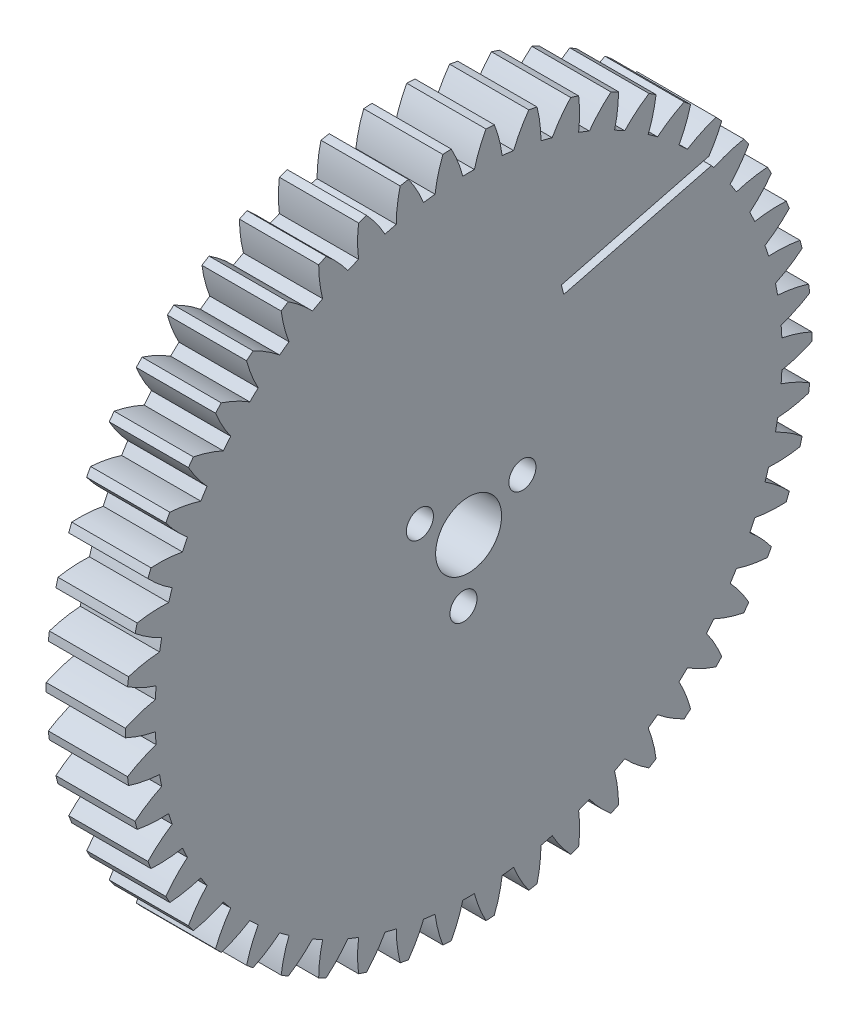
SolidWorks part; units mm, degrees
ref_plane "Plane1" through (0, 0, 0) normal (0, 0, 1) x (1, 0, 0)
ref_plane "Plane2" through (0, 0, 0) normal (0, 1, 0) x (1, 0, 0)
ref_plane "Plane3" through (0, 0, 0) normal (1, 0, 0) x (0, 0, -1)
sketch "HoldingSke" plane through (0, 0, 0) normal (0, 1, 0) x (1, 0, 0)
  line L0 (0, 0) -> (0.6428, -0.766)
  line L1 (-15, 0) -> (100, 0) construction
  line L2 (0, 0) -> (-2.1039, 2.3779)
  line L3 (0, 0) -> (-11.863, 4.5341)
  line L4 (0, 0) -> (5.5511, 6.6156)
  line L5 (0, 0) -> (-46.8476, -17.4728)
  line L6 (0, 0) -> (-3.3159, -2.2372)
  line L7 (-2.1039, 2.3779) -> (8.6586, 51.2059)
  line L8 (-76.2, 54.61) -> (-75.3, 54.61)
  line L9 (-71.009, 38.7566) -> (-53.1078, 45.2721)
  line L10 (-76.2, 71.12) -> (104.1128, 71.12)
  line L11 (0, 0) -> (-4, 0)
  line L12 (-76.2, 101.6) -> (-76.162, 101.6)
  line L13 (24.9733, 27.94) -> (52.9518, 28.4284)
  line L14 (24.9733, 27.94) -> (24.9743, 27.94)
  line L15 (24.9733, 27.94) -> (100.4006, 29.5858)
  line L16 (-63.627, -1) -> (-12.827, -1)
  circle A0 centre (0, 0) radius 2.5
  circle A1 centre (0, 0) radius 23.749
  circle A2 centre (0, 0) radius 37.5
  circle A3 centre (0, 0) radius 2.5
  dimension "MHD" = 47.498
  dimension "Hub_dia" = 75
  dimension "Bore" = 5
  dimension "MBD" = 5
  dimension "Num_teeth" = 50
  dimension "Pitch_radius" = 180.3128
  dimension "Pitch" = 1
  dimension "Width" = 4
  dimension "Overall_len" = 50
  dimension "Show_teeth" = 50
  dimension "Thickness" = 4
  dimension "OAL" = 50.0001
  dimension "T_dim" = 0.9
  dimension "Ap" = 20
  dimension "H" = 19.05
  dimension "Backlash" = 0.038
  dimension "Addendum_fac" = 1
  dimension "Dedendum_fac" = 1.25
  dimension "Clearance_fac" = 0.25
  dimension "Dedendum_add" = 0.001
  dimension "Module" = 1
sketch "BasProSke" plane through (0, 0, 0) normal (0, 1, 0) x (1, 0, 0)
  line L0 (-10, 0) -> (60, 0) construction
  line L1 (0, 0) -> (0, 26)
  line L2 (0, 0) -> (6, 0)
  line L3 (6, 0) -> (6, 26)
  line L4 (6, 26) -> (0, 26)
  dimension "Diameter" = 52
  dimension "Thickness" = 6
revolve "Base-Revolve" add sketch "BasProSke" angle 360 about L0
sketch "TooCutSke" plane through (0, 0, 0) normal (1, 0, 0) x (0, 0, -1)
  line L1 (0, 0) -> (0, 107) construction
  line L2 (0, 0) -> (-0.8518, 24.9855) construction
  line L3 (0, 0) -> (-3.1382, 49.8807) construction
  line L4 (-0.8518, 24.9855) -> (-1.5691, 24.9404) construction
  arc A0 (0.4377, 23.745) -> (-0.4377, 23.745) centre (0, 0) ccw
  arc A1 (1.3294, 25.9914) -> (-1.3294, 25.9914) centre (0, 0) ccw
  circle A2 centre (0, 0) radius 25 construction
  circle A3 centre (0, 0) radius 23.4923 construction
  arc A4 (-0.4377, 23.745) -> (-1.3294, 25.9914) centre (-10.1099, 21.2056) ccw
  arc A5 (1.3294, 25.9914) -> (0.4377, 23.745) centre (10.1099, 21.2056) ccw
  dimension "Root_dia" = 47.498
  dimension "Overcut_dia" = 52.0508
  dimension "Pitch_dia" = 50
  dimension "Base_dia" = 46.9846
  dimension "Flank_rad" = 10
  dimension "Half_ang" = 3.6
  dimension "Half_CT" = 0.7188
extrude "ToothCut" cut sketch "TooCutSke" along normal through all
fillet "Breaks" [suppressed] radius 0.02 tangent propagation no
fillet "RootFillets" [suppressed] radius 0.251
pattern_circular "TeethCuts" count 50 every 7.2 about axis through (-10, 0, 0) along (1, 0, 0) of "ToothCut", "RootFillets", "Breaks"
sketch "HubNeaOneSke" plane through (0, 0, 0) normal (-1, 0, 0) x (0, 0, 1)
  circle A0 centre (0, 0) radius 23.749
  dimension "Diameter" = 47.498
extrude "HubNearOne" [suppressed] add sketch "HubNeaOneSke" along normal blind 44.0001
sketch "HubNeaBotSke" plane through (0, 0, 0) normal (-1, 0, 0) x (0, 0, 1)
  circle A0 centre (0, 0) radius 23.749
  dimension "Diameter" = 47.498
extrude "HubNearBoth" [suppressed] add sketch "HubNeaBotSke" along normal blind 22
ref_plane "FarPln" through (6, 0, 0) normal (1, 0, 0) x (0, 0, -1)
sketch "HubFarSke" plane through (6, 0, 0) normal (1, 0, 0) x (0, 0, -1)
  circle A0 centre (0, 0) radius 23.749
  dimension "Diameter" = 47.498
extrude "HubFar" [suppressed] add sketch "HubFarSke" along normal blind 22
sketch "BorSke" plane through (0, 0, 0) normal (1, 0, 0) x (0, 0, -1)
  circle A0 centre (0, 0) radius 2.5
  dimension "Diameter" = 5
extrude "Bore" cut sketch "BorSke" along normal mid plane 100.0001
sketch "KeySke" plane through (0, 0, 0) normal (1, 0, 0) x (0, 0, -1)
  line L0 (-1, 0) -> (-1, 3.4)
  line L1 (-1, 3.4) -> (1, 3.4)
  line L2 (1, 3.4) -> (1, 0)
  line L3 (0, 0) -> (0, 34) construction
  line L4 (-1, 0) -> (1, 0)
  dimension "Offset" = 3.4
  dimension "Width" = 2
extrude "Keyway" [suppressed] cut sketch "KeySke" along normal mid plane 100.0001
pattern_circular "Keyway2" [suppressed] count 2 every 90 about axis through (-10, 0, 0) along (1, 0, 0)
hole_wizard "Ø2.05 (2.05) Diameter Hole1" positions "Sketch1" profile "Sketch2" hole size "Ø2.05" standard "ISO" end condition through all
sketch "Sketch1" plane through (-8.7955, -164.7867, -27.9652) normal (-1, 0, 0) x (0, 0, 1)
  circle A0 centre (27.9652, 164.7867) radius 4.5
  point P0 (23.8893, 166.6937)
  point P2 (31.6547, 167.3631)
  point P4 (28.3517, 160.3033)
sketch "Sketch2" plane through (-8.7955, 1.907, -4.0759) normal (0, 1, 0) x (0, 0, 1)
  line L0 (0, 0) -> (0, 14.7955)
  line L1 (0, 14.7955) -> (1.025, 14.7955)
  line L2 (1.025, 14.7955) -> (1.025, 0)
  line L3 (1.025, 0) -> (0, 0)
  line L4 (0, -6.35) -> (0, 107.95) construction
  dimension "Thru Hole Dia." = 2.05
  dimension "Thru Hole Depth" = 14.7955
extrude "Cut-Extrude1" cut sketch "Sketch3" against normal through all
sketch "Sketch3" plane through (97.0946, -158.9017, -50.9706) normal (0, -0.2478, 0.9688) x (1, 0, 0)
  line L0 (-97.2608, 177.3132) -> (-97.2608, 176.5766)
  line L1 (-97.2608, 177.3132) -> (-90.708, 177.3132)
  line L2 (-97.2608, 176.5766) -> (-90.708, 176.5766)
  line L3 (-90.708, 177.3132) -> (-90.708, 176.5766)
equation "' \"Module@HoldingSke\" = 6.35"
equation "' \"Num_teeth@HoldingSke\" = 12"
equation "' \"Ap@HoldingSke\" =  20"
equation "' \"Width@HoldingSke\" = 0.5 * 25.4"
equation "' \"Hub_dia@HoldingSke\"= 1 * 25.4"
equation "' \"Overall_len@HoldingSke\" = 1.0 * 25.4"
equation "' \"Bore@HoldingSke\" = 0.75 * 25.4"
equation "' \"T_dim@HoldingSke\" = 0.1 * 25.4"
equation "' \"Width@KeySke\" = 0.25 * 25.4"
equation "' \"Show_teeth@HoldingSke\" = 13"
equation "' \"Backlash@HoldingSke\" = 0.009 * 25.4"
equation "' \"Addendum_fac@HoldingSke\" = 1.0"
equation "' \"Dedendum_fac@HoldingSke\" = 1.25"
equation "' \"Dedendum_add@HoldingSke\" = 0.00005 * 25.4"
equation "' \"Clearance_fac@HoldingSke\" = 0.25"
equation "\"Pitch@HoldingSke\" = 1 / \"Module@HoldingSke\""
equation "\"Overcut_dia@TooCutSke\" = (\"Num_teeth@HoldingSke\" + 2 * \"Addendum_fac@HoldingSke\") / \"Pitch@HoldingSke\" + 0.002 * 25.4"
equation "\"Pitch_dia@TooCutSke\" = \"Num_teeth@HoldingSke\" / \"Pitch@HoldingSke\""
equation "\"Base_dia@TooCutSke\" = \"Num_teeth@HoldingSke\" / \"Pitch@HoldingSke\" * cos((\"Ap@HoldingSke\"  * 3.14159265 / 180))"
equation "\"Root_dia@TooCutSke\" = (\"Num_teeth@HoldingSke\" + 2) / \"Pitch@HoldingSke\" - 2 * (\"Addendum_fac@HoldingSke\" + \"Dedendum_fac@HoldingSke\") / \"Pitch@HoldingSke\" - \"Dedendum_add@HoldingSke\" * 2"
equation "\"Half_ang@TooCutSke\" = 180 / \"Num_teeth@HoldingSke\""
equation "\"Half_CT@TooCutSke\" = \"Num_teeth@HoldingSke\" / \"Pitch@HoldingSke\" * sin((3.14159265 / 2 / \"Num_teeth@HoldingSke\")) / 2 - 7 * \"Backlash@HoldingSke\" / 4"
equation "\"Flank_rad@TooCutSke\" = \"Num_teeth@HoldingSke\" / \"Pitch@HoldingSke\" / 5"
equation "\"Radius@RootFillets\" = \"Clearance_fac@HoldingSke\" / \"Pitch@HoldingSke\" + \"Dedendum_add@HoldingSke\""
equation "\"Break_rad@Breaks\" = 0.02 / \"Pitch@HoldingSke\""
equation "\"Thickness@HoldingSke\" = \"Width@HoldingSke\""
equation "\"OAL@HoldingSke\" = \"Thickness@HoldingSke\""
equation "\"MHD@HoldingSke\" = (\"Num_teeth@HoldingSke\" + 2) / \"Pitch@HoldingSke\" - 2 * (\"Addendum_fac@HoldingSke\" + \"Dedendum_fac@HoldingSke\")  / \"Pitch@HoldingSke\" - \"Dedendum_add@HoldingSke\" * 2"
equation "\"MBD@HoldingSke\" = (\"Num_teeth@HoldingSke\" + 2) / \"Pitch@HoldingSke\" - 2 * (\"Addendum_fac@HoldingSke\" + \"Dedendum_fac@HoldingSke\")  / \"Pitch@HoldingSke\" - \"Dedendum_add@HoldingSke\" * 2 - 0.002 * 25.4"
equation "\"MHD@HoldingSke\" = ((sgn( \"MHD@HoldingSke\" - \"Hub_dia@HoldingSke\" )-1)*( \"MHD@HoldingSke\" - \"Hub_dia@HoldingSke\" ))/-2+ \"Hub_dia@HoldingSke\""
equation "\"MBD@HoldingSke\" = ((sgn( \"MBD@HoldingSke\" - \"Bore@HoldingSke\" )-1)*( \"MBD@HoldingSke\" - \"Bore@HoldingSke\" ))/-2+ \"Bore@HoldingSke\""
equation "\"OAL@HoldingSke\" = ((sgn( \"OAL@HoldingSke\" - \"Overall_len@HoldingSke\" )+1)*( \"OAL@HoldingSke\" - \"Overall_len@HoldingSke\" ))/2 + \"Overall_len@HoldingSke\" + 0.000002 * 25.4"
equation "\"Num_teeth@TeethCuts\" = int( \"Show_teeth@HoldingSke\" ) + 1"
equation "\"Num_teeth@TeethCuts\" = ((sgn( \"Num_teeth@TeethCuts\" - \"Num_teeth@HoldingSke\" )-1)*( \"Num_teeth@TeethCuts\" - \"Num_teeth@HoldingSke\" ))/-2+ \"Num_teeth@HoldingSke\""
equation "\"Num_teeth@TeethCuts\" = ((sgn( \"Num_teeth@TeethCuts\" - 2.0)+1)*( \"Num_teeth@TeethCuts\" - 2.0))/2 +2.0"
equation "\"Angle@TeethCuts\" = 360.0 / \"Num_teeth@HoldingSke\""
equation "\"Diameter@BasProSke\" = (\"Num_teeth@HoldingSke\" + 2 * \"Addendum_fac@HoldingSke\") / \"Pitch@HoldingSke\""
equation "' \"Fillet_rad@BasProSke\" =  \"Thickness@HoldingSke\" * 0.05"
equation "\"MHD@HoldingSke\" = ((sgn( \"MHD@HoldingSke\" - \"Root_dia@TooCutSke\" )-1)*( \"MHD@HoldingSke\" - \"Root_dia@TooCutSke\" ))/-2+ \"Root_dia@TooCutSke\""
equation "\"Diameter@HubNeaOneSke\" = \"MHD@HoldingSke\""
equation "\"Length@HubNearOne\" = \"OAL@HoldingSke\" - \"Thickness@BasProSke\""
equation "\"Diameter@HubNeaBotSke\" = \"MHD@HoldingSke\""
equation "\"Length@HubNearBoth\" = ( \"OAL@HoldingSke\" - \"Thickness@BasProSke\" ) / 2.0"
equation "\"Thickness@FarPln\" = \"Thickness@BasProSke\""
equation "\"Diameter@HubFarSke\" = \"MHD@HoldingSke\""
equation "\"Length@HubFar\" = ( \"OAL@HoldingSke\" - \"Thickness@BasProSke\" ) / 2.0"
equation "\"Diameter@BorSke\" = \"MBD@HoldingSke\""
equation "\"D1@Bore\" = \"OAL@HoldingSke\" * 2.0"
equation "\"D1@Keyway\" = \"OAL@HoldingSke\" * 2.0"
equation "\"Offset@KeySke\" = \"T_dim@HoldingSke\" + \"MBD@HoldingSke\" / 2.0"
